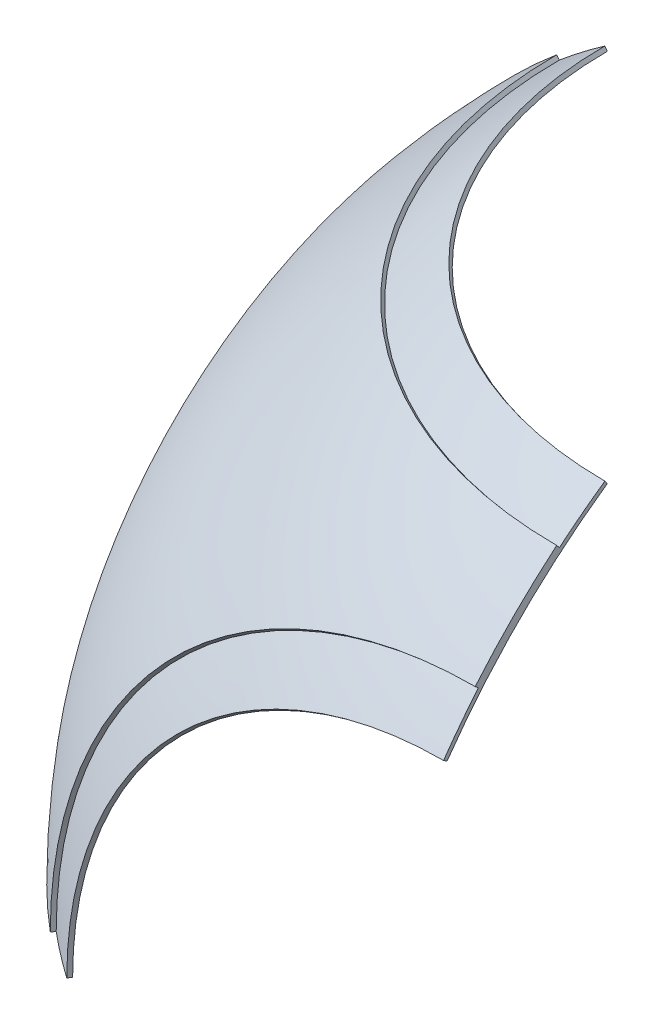
SolidWorks part; units mm, degrees
ref_plane "Front Plane" through (0, 0, 0) normal (0, 0, 1) x (1, 0, 0)
ref_plane "Top Plane" through (0, 0, 0) normal (0, 1, 0) x (1, 0, 0)
ref_plane "Right Plane" through (0, 0, 0) normal (1, 0, 0) x (0, 0, -1)
sketch "Sketch1" plane through (0, 0, 0) normal (0, 0, 1) x (1, 0, 0)
  line L0 (0, 0) -> (0, 309.9271)
  line L1 (0, 309.9271) -> (0, 0)
  line L2 (-246.825, 0) -> (-250, 0)
  line L3 (-141.573, 202.1872) -> (-142.4836, 203.4876)
  line L4 (-159.6765, 190.295) -> (-160.6969, 191.5111)
  arc A0 (-160.6969, 191.5111) -> (-250, 0) centre (0, 0) ccw
  arc A1 (-141.573, 202.1872) -> (-246.825, 0) centre (0, 0) ccw
  arc A2 (-142.4836, 203.4876) -> (-159.6765, 190.295) centre (0, 0) ccw
  dimension "D1" = 500
  dimension "D2" = 493.65
  dimension "D3" = 496.825
  dimension "D4" = 35
  dimension "D5" = 5
revolve "Revolve1" add sketch "Sketch1" angle 90 about L0 region at (-248.4125, 2.3057, 0)
sketch "Sketch3" plane through (0, 0, 0) normal (1, 0, 0) x (0, 0, -1)
  line L0 (-246.825, 0) -> (-250, 0)
  line L1 (-202.1872, 141.573) -> (-203.4876, 142.4836)
  line L2 (-190.295, 159.6765) -> (-191.5111, 160.6969)
  arc A0 (-190.295, 159.6765) -> (-203.4876, 142.4836) centre (0, 0) ccw
  arc A1 (-141.573, 202.1872) -> (-246.825, 0) centre (0, 0) ccw construction
  arc A2 (-202.1872, 141.573) -> (-246.825, 0) centre (0, 0) ccw
  arc A3 (-160.6969, 191.5111) -> (-250, 0) centre (0, 0) ccw construction
  arc A4 (-191.5111, 160.6969) -> (-250, 0) centre (0, 0) ccw
  dimension "D1" = 496.825
  dimension "D2" = 5
  dimension "D3" = 35
revolve "Cut-Revolve1" cut sketch "Sketch3" angle 360 about L0
sketch "Sketch4" plane through (0, 0, 0) normal (0, 0, -1) x (-1, 0, 0)
  line L0 (246.825, 0) -> (250, 0)
  line L1 (202.1872, 141.573) -> (203.4876, 142.4836)
  line L2 (190.295, 159.6765) -> (191.5111, 160.6969)
  arc A0 (203.4876, 142.4836) -> (190.295, 159.6765) centre (0, 0) ccw
  arc A1 (246.825, 0) -> (141.573, 202.1872) centre (0, 0) ccw construction
  arc A2 (246.825, 0) -> (202.1872, 141.573) centre (0, 0) ccw
  arc A3 (250, 0) -> (160.6969, 191.5111) centre (0, 0) ccw construction
  arc A4 (250, 0) -> (191.5111, 160.6969) centre (0, 0) ccw
  dimension "D1" = 496.825
  dimension "D2" = 5
  dimension "D3" = 35
revolve "Cut-Revolve2" cut sketch "Sketch4" angle 360 about L0
